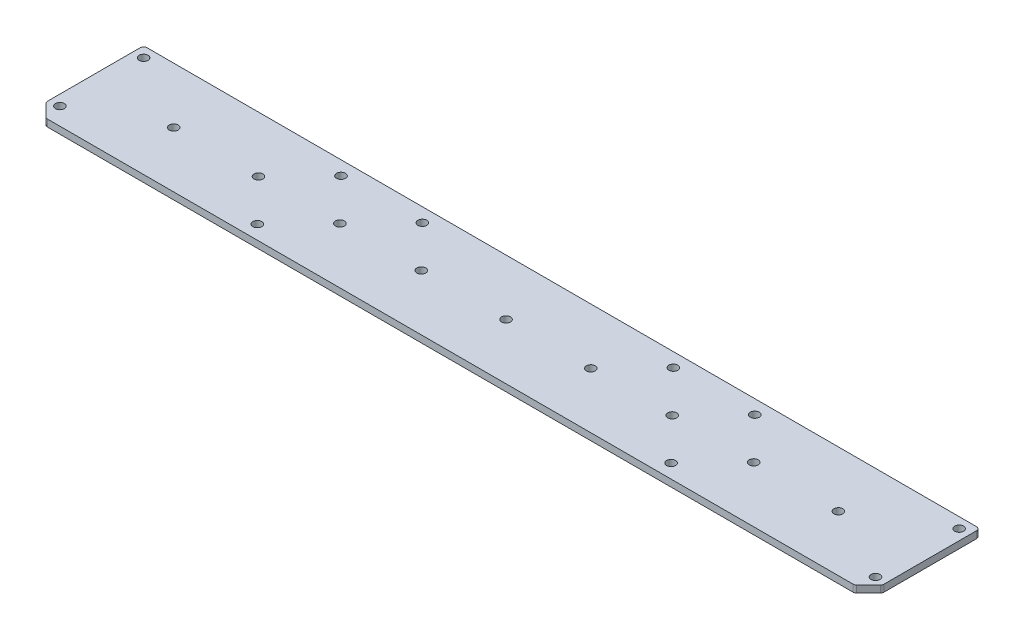
SolidWorks part; units mm, degrees
ref_plane "Front Plane" through (0, 0, 0) normal (0, 0, 1) x (1, 0, 0)
ref_plane "Top Plane" through (0, 0, 0) normal (0, 1, 0) x (1, 0, 0)
ref_plane "Right Plane" through (0, 0, 0) normal (1, 0, 0) x (0, 0, -1)
sketch "Sketch2" plane through (0, 0, 0) normal (0, 1, 0) x (1, 0, 0)
  line L0 (0, 7.0076) -> (0, 50.8)
  line L1 (0, 50.8) -> (381, 50.8)
  line L2 (381, 50.8) -> (381, 7.0076)
  line L3 (373.9924, 0) -> (7.0076, 0)
  line L4 (5.885, 0.465) -> (0.465, 5.885) construction
  line L5 (5.885, 0.465) -> (0.465, 5.885)
  line L6 (375.115, 0.465) -> (380.535, 5.885) construction
  line L7 (375.115, 0.465) -> (380.535, 5.885)
  line L8 (336.5758, 50.8) -> (379.4125, 50.8) construction
  arc A0 (5.885, 0.465) -> (7.0076, 0) centre (7.0076, 1.5875) ccw construction
  arc A1 (0, 7.0076) -> (0.465, 5.885) centre (1.5875, 7.0076) ccw construction
  arc A2 (5.885, 0.465) -> (7.0076, 0) centre (7.0076, 1.5875) ccw
  arc A3 (0, 7.0076) -> (0.465, 5.885) centre (1.5875, 7.0076) ccw
  arc A4 (373.9924, 0) -> (375.115, 0.465) centre (373.9924, 1.5875) ccw construction
  arc A6 (373.9924, 0) -> (375.115, 0.465) centre (373.9924, 1.5875) ccw
  arc A8 (380.535, 5.885) -> (381, 7.0076) centre (379.4125, 7.0076) ccw construction
  arc A9 (380.535, 5.885) -> (381, 7.0076) centre (379.4125, 7.0076) ccw
extrude "Boss-Extrude1" add sketch "Sketch2" along normal blind 3.175
sketch "Sketch3" plane through (0, 0, 0) normal (0, 1, 0) x (1, 0, 0)
  circle A25 centre (4.7625, 7.9375) radius 2.032 construction
  circle A31 centre (4.7625, 46.0375) radius 2.032 construction
  circle A63 centre (376.2375, 7.9375) radius 2.032 construction
  circle A64 centre (376.2375, 46.0375) radius 2.032 construction
  circle A67 centre (4.7625, 7.9375) radius 2.032
  circle A68 centre (4.7625, 46.0375) radius 2.032
  circle A72 centre (376.2375, 7.9375) radius 2.032
  circle A73 centre (376.2375, 46.0375) radius 2.032
  circle A123 centre (341.884, 25.4) radius 2.032 construction
  circle A124 centre (247.65, 44.45) radius 2.032 construction
  circle A125 centre (284.734, 44.45) radius 2.032 construction
  circle A129 centre (284.734, 6.35) radius 2.032 construction
  circle A132 centre (190.5, 25.4) radius 2.032 construction
  circle A135 centre (133.35, 44.45) radius 2.032 construction
  circle A136 centre (96.266, 44.45) radius 2.032 construction
  circle A137 centre (96.266, 6.35) radius 2.032 construction
  circle A140 centre (77.724, 25.4) radius 2.032 construction
  circle A141 centre (39.116, 25.4) radius 2.032 construction
  circle A142 centre (341.884, 25.4) radius 2.032
  circle A143 centre (247.65, 44.45) radius 2.032
  circle A144 centre (284.734, 44.45) radius 2.032
  circle A148 centre (284.734, 6.35) radius 2.032
  circle A151 centre (190.5, 25.4) radius 2.032
  circle A154 centre (133.35, 44.45) radius 2.032
  circle A155 centre (96.266, 44.45) radius 2.032
  circle A156 centre (96.266, 6.35) radius 2.032
  circle A159 centre (77.724, 25.4) radius 2.032
  circle A160 centre (39.116, 25.4) radius 2.032
  circle A161 centre (151.892, 25.4) radius 2.032
  circle A162 centre (229.108, 25.4) radius 2.032
  circle A163 centre (266.192, 25.4) radius 2.032
  circle A164 centre (303.276, 25.4) radius 2.032
  circle A165 centre (151.892, 25.4) radius 2.3813 construction
  circle A166 centre (229.108, 25.4) radius 2.3813 construction
  circle A167 centre (266.192, 25.4) radius 2.3813 construction
  circle A168 centre (303.276, 25.4) radius 2.3813 construction
  circle A170 centre (114.808, 25.4) radius 2.032 construction
  circle A171 centre (114.808, 25.4) radius 2.032
extrude "Cut-Extrude1" cut sketch "Sketch3" along normal through all
fillet "Fillet1" radius 1.5875 2 edges at (0, 1.5875, -50.8) (381, 1.5875, -50.8)
